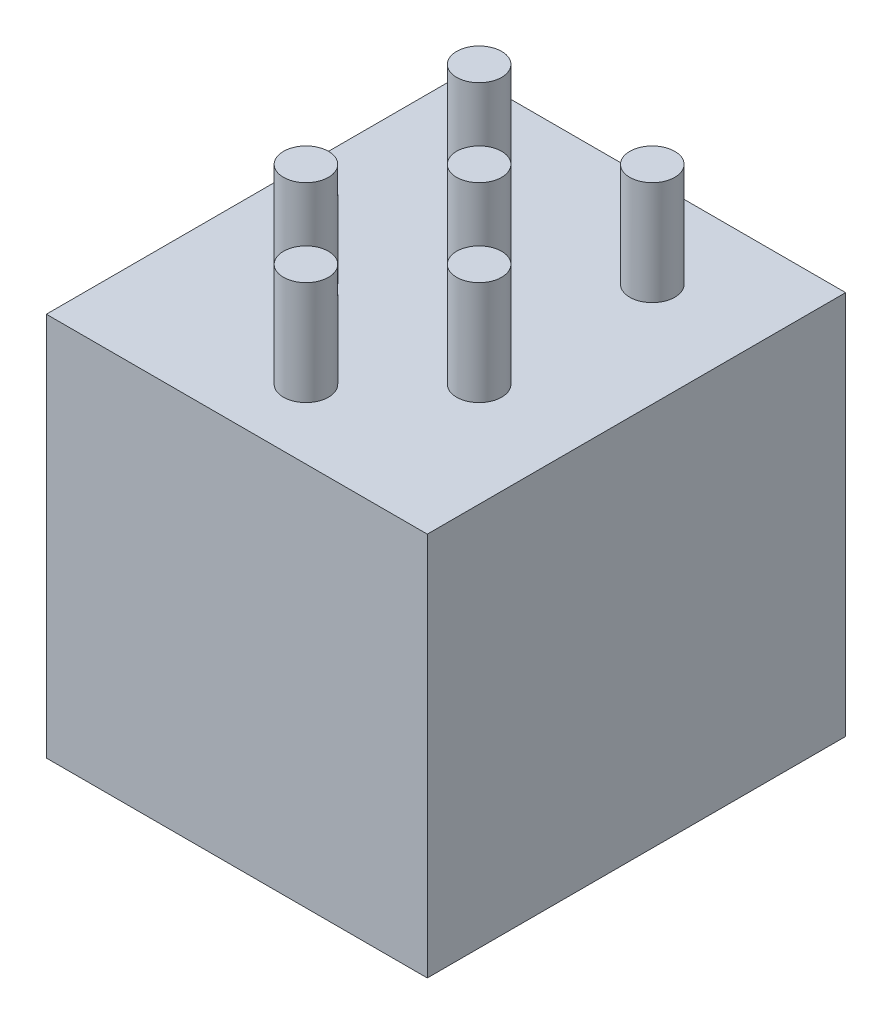
SolidWorks part; units mm, degrees
ref_plane "Front Plane" through (0, 0, 0) normal (0, 0, 1) x (1, 0, 0)
ref_plane "Top Plane" through (0, 0, 0) normal (0, 1, 0) x (1, 0, 0)
ref_plane "Right Plane" through (0, 0, 0) normal (1, 0, 0) x (0, 0, -1)
sketch "Sketch1" plane through (0, 0, 0) normal (0, 1, 0) x (1, 0, 0)
  line L1 (-5.5, -6.04) -> (5.5, -6.04)
  line L2 (-5.5, -6.04) -> (-5.5, 6.04)
  line L3 (-5.5, 6.04) -> (5.5, 6.04)
  line L4 (5.5, -6.04) -> (5.5, 6.04)
  line L5 (-5.5, -6.04) -> (5.5, 6.04) construction
  line L6 (-5.5, 6.04) -> (5.5, -6.04) construction
  point P0 (0, 0)
  dimension "D1" = 11
  dimension "D2" = 12.08
extrude "Boss-Extrude1" add sketch "Sketch1" along normal blind 11.1
sketch "Sketch3" plane through (0, 11.1, 0) normal (0, 1, 0) x (1, 0, 0)
  line L0 (-2.5, -1.5436) -> (2.5, 3.4564) construction
  line L1 (-2.5, 3.4564) -> (2.5, -1.5436) construction
  line L2 (5.5, 6.04) -> (-5.5, 6.04) construction
  circle A0 centre (0, -4.0436) radius 0.65
  circle A1 centre (2.5, -1.5436) radius 0.65
  circle A2 centre (-2.5, -1.5436) radius 0.65
  circle A3 centre (-2.5, 3.4564) radius 0.65
  circle A4 centre (2.5, 3.4564) radius 0.65
  circle A5 centre (0, 0.9564) radius 0.65
  point P13 (0, 6.04)
  dimension "D4" = 5
  dimension "D6" = 1.3
  dimension "D3" = 5
  dimension "D5" = 5
  dimension "D1" = 2
  dimension "D2" = 2
extrude "Boss-Extrude2" add sketch "Sketch3" along normal blind 3
